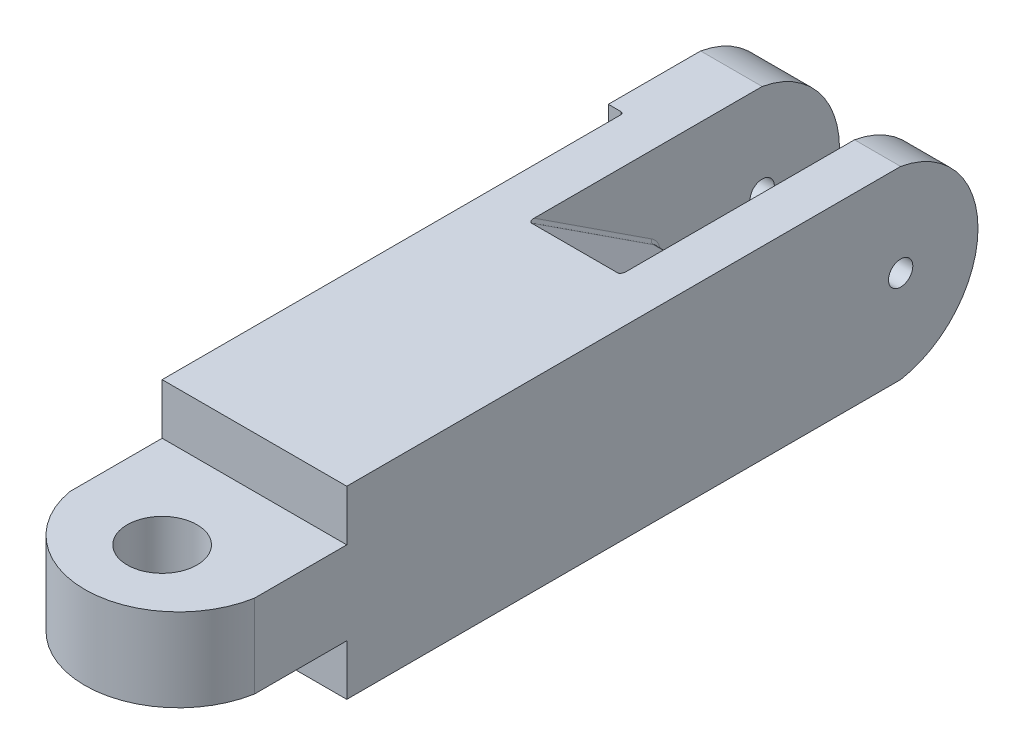
SolidWorks part; units mm, degrees
ref_plane "Front Plane" through (0, 0, 0) normal (0, 0, 1) x (1, 0, 0)
ref_plane "Top Plane" through (0, 0, 0) normal (0, 1, 0) x (1, 0, 0)
ref_plane "Right Plane" through (0, 0, 0) normal (1, 0, 0) x (0, 0, -1)
sketch "Sketch2" plane through (0, 0, 0) normal (0, 0, 1) x (1, 0, 0)
  line L1 (-30, 30) -> (30, 30)
  line L2 (-30, 30) -> (-30, -30)
  line L3 (-30, -30) -> (30, -30)
  line L4 (30, 30) -> (30, -30)
  line L5 (-30, 30) -> (30, -30) construction
  line L6 (-30, -30) -> (30, 30) construction
  point P0 (0, 0)
  dimension "D1" = 60
  dimension "D2" = 60
extrude "Boss-Extrude1" add sketch "Sketch2" along normal blind 150
ref_plane "Plane1" through (0, 0, 0) normal (0, 0, -1) x (-1, 0, 0)
sketch "Sketch3" plane through (0, 0, 0) normal (0, 0, -1) x (-1, 0, 0)
  line L0 (-30, 30) -> (30, 30) construction
  line L1 (30, -30) -> (15, -30)
  line L2 (30, -30) -> (30, 30)
  line L3 (30, 30) -> (15, 30)
  line L4 (15, -30) -> (15, 30)
  line L5 (30, -30) -> (-30, -30) construction
  line L6 (-30, 30) -> (-15, 30)
  line L7 (-30, 30) -> (-30, -30)
  line L8 (-30, -30) -> (-15, -30)
  line L9 (-15, 30) -> (-15, -30)
  dimension "D1" = 15
  dimension "D2" = 15
extrude "Boss-Extrude2" add sketch "Sketch3" along normal blind 30
ref_plane "Plane2" through (30, 0, 0) normal (1, 0, 0) x (0, 0, -1)
sketch "Sketch4" plane through (30, 0, 0) normal (1, 0, 0) x (0, 0, -1)
  line L0 (30, 30) -> (30, -30)
  arc A0 (30, 30) -> (30, -30) centre (24.6689, 0) cw
  dimension "D1" = 30.47
extrude "Boss-Extrude3" add sketch "Sketch4" against normal blind 15
ref_plane "Plane3" through (-30, 0, 0) normal (-1, 0, 0) x (0, 0, 1)
sketch "Sketch5" plane through (-30, 0, 0) normal (-1, 0, 0) x (0, 0, 1)
  line L0 (-30, -30) -> (-30, 30)
  arc A0 (-30, -30) -> (-30, 30) centre (-24.6689, 0) cw
  dimension "D1" = 30.47
extrude "Boss-Extrude4" add sketch "Sketch5" against normal blind 15
ref_plane "Plane4" through (0, 0, 150) normal (0, 0, 1) x (1, 0, 0)
sketch "Sketch6" plane through (0, 0, 150) normal (0, 0, 1) x (1, 0, 0)
  line L0 (30, -30) -> (30, 30) construction
  line L1 (-30, 13.5) -> (30, 13.5)
  line L2 (-30, 13.5) -> (-30, -13.5)
  line L3 (-30, -13.5) -> (30, -13.5)
  line L4 (30, 13.5) -> (30, -13.5)
  line L5 (-30, 13.5) -> (30, -13.5) construction
  line L6 (-30, -13.5) -> (30, 13.5) construction
  point P0 (0, 0)
  dimension "D1" = 27
extrude "Boss-Extrude5" add sketch "Sketch6" along normal blind 30
ref_plane "Plane5" through (0, 13.5, 0) normal (0, 1, 0) x (1, 0, 0)
sketch "Sketch7" plane through (0, 13.5, 0) normal (0, 1, 0) x (1, 0, 0)
  line L0 (30, -180) -> (-30, -180)
  arc A0 (30, -180) -> (-30, -180) centre (0, -174.6689) cw
  dimension "D1" = 30.47
extrude "Boss-Extrude6" add sketch "Sketch7" against normal blind 27
ref_plane "Plane6" through (0, 0, 150) normal (0, 0, 1) x (1, 0, 0)
sketch "Sketch8" plane through (0, 0, 150) normal (0, 0, 1) x (1, 0, 0)
  line L1 (-25.25, -25.25) -> (25.25, -25.25)
  line L2 (-25.25, -25.25) -> (-25.25, 25.25)
  line L3 (-25.25, 25.25) -> (25.25, 25.25)
  line L4 (25.25, -25.25) -> (25.25, 25.25)
  line L5 (-25.25, -25.25) -> (25.25, 25.25) construction
  line L6 (-25.25, 25.25) -> (25.25, -25.25) construction
  point P0 (0, 0)
  dimension "D1" = 50.5
  dimension "D2" = 50.5
extrude "Cut-Extrude2" cut sketch "Sketch8" against normal blind 70 and the other way blind 5 from offset 10 contours L3 L4 L1 L2 offset against normal yes
ref_plane "Plane7" through (0, -13.5, 0) normal (0, -1, 0) x (-1, 0, 0)
sketch "Sketch9" plane through (0, -13.5, 0) normal (0, -1, 0) x (-1, 0, 0)
  line L0 (30, -150) -> (-30, -150) construction
  circle A0 centre (0, -180) radius 11.35
  dimension "D1" = 22.7
  dimension "D2" = 30
extrude "Cut-Extrude3" cut sketch "Sketch9" against normal blind 130
ref_plane "Plane8" through (30, 0, 0) normal (1, 0, 0) x (0, 0, -1)
ref_plane "Plane9" through (15, 0, 0) normal (-1, 0, 0) x (0, 0, 1)
sketch "Sketch11" plane through (15, 0, 0) normal (-1, 0, 0) x (0, 0, 1)
  line L0 (0, -30) -> (0, 30) construction
  circle A0 centre (-30, 0) radius 3.95
  dimension "D2" = 7.9
  dimension "D1" = 30
extrude "Cut-Extrude4" cut sketch "Sketch11" against normal through all
ref_plane "Plane10" through (-15, 0, 0) normal (1, 0, 0) x (0, 0, -1)
sketch "Sketch12" plane through (-15, 0, 0) normal (1, 0, 0) x (0, 0, -1)
  line L0 (0, 30) -> (0, -30) construction
  circle A0 centre (30, 0) radius 3.95
  dimension "D1" = 30
  dimension "D2" = 7.9
extrude "Cut-Extrude5" cut sketch "Sketch12" against normal through all
ref_plane "Plane11" through (0, 30, 0) normal (0, 1, 0) x (1, 0, 0)
ref_plane "Plane12" through (-30, 0, 0) normal (-1, 0, 0) x (0, 0, 1)
sketch "Sketch13" plane through (-30, 0, 0) normal (-1, 0, 0) x (0, 0, 1)
  line L0 (-30, 30) -> (0, 30)
  line L1 (150, 30) -> (-30, 30) construction
  line L2 (0, 30) -> (0, -30)
  line L3 (150, -30) -> (-30, -30) construction
  line L4 (0, -30) -> (-30, -30)
  arc A0 (-30, 30) -> (-30, -30) centre (-24.6689, 0) ccw
  dimension "D1" = 30
extrude "Boss-Extrude7" add sketch "Sketch13" along normal blind 5
ref_plane "Plane13" through (-35, 0, 0) normal (-1, 0, 0) x (0, 0, 1)
sketch "Sketch14" plane through (-35, 0, 0) normal (-1, 0, 0) x (0, 0, 1)
  line L0 (0, -30) -> (0, 30) construction
  circle A0 centre (-30, 0) radius 4.15
  dimension "D1" = 8.3
  dimension "D2" = 30
extrude "Cut-Extrude6" cut sketch "Sketch14" against normal blind 10
fillet "Fillet2" radius 1 1 edges at (-30, 0, 0)
ref_plane "Plane14" through (0, -30, 0) normal (0, -1, 0) x (-1, 0, 0)
sketch "Sketch19" plane through (15, 0, 0) normal (-1, 0, 0) x (0, 0, 1)
  line L0 (150, 30) -> (1, 30) construction
  line L1 (0, -30) -> (45.937, -30)
  line L2 (0, -30) -> (0, 30)
  line L3 (0, 30) -> (45.937, 30)
  line L5 (0, 0) -> (45.937, -30)
  line L6 (0, 0) -> (45.937, 30)
  line M3 (0, -30) -> (0, 30)
extrude "Cut-Extrude8" cut sketch "Sketch19" along normal blind 30 contours L2 L6 L3 | L5 L1 M3 | L2 L3 L6 L5 L1 region at (15, -20, 15.3123) region at (15, 20, 15.3123)
fillet "Fillet7" radius 5 1 edges at (0, 0, 0)
fillet "Fillet8" radius 1 3 edges at (15, -17.0932, 26.1736) (15, 0, 4.1442) (15, 17.0932, 26.1736)
fillet "Fillet9" radius 1 3 edges at (-15, -17.0932, 26.1736) (-15, 0, 4.1442) (-15, 17.0932, 26.1736)
